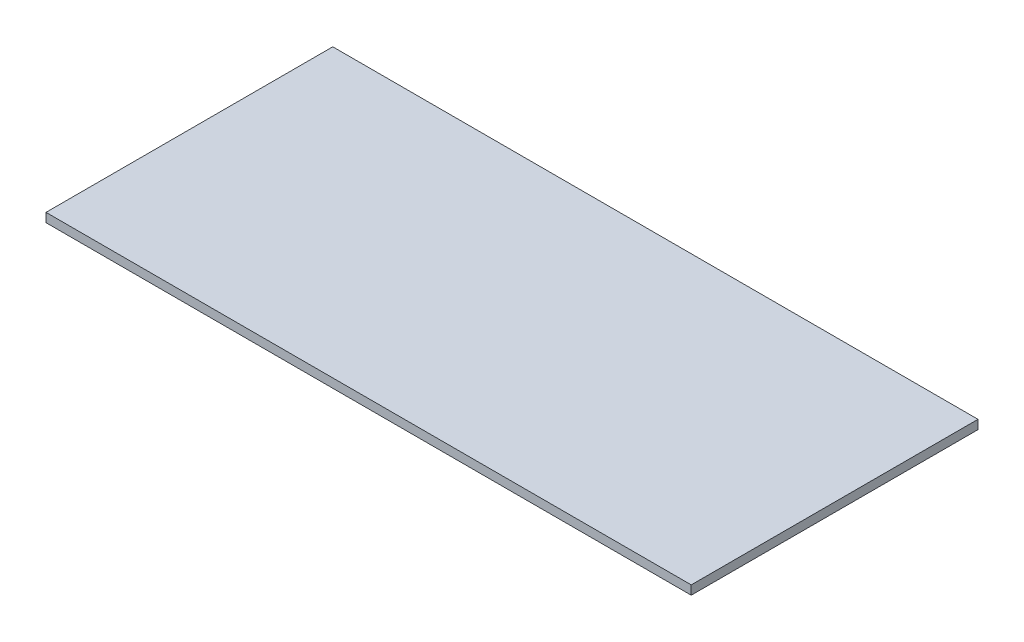
SolidWorks part; units mm, degrees
ref_plane "Front Plane" through (0, 0, 0) normal (0, 0, 1) x (1, 0, 0)
ref_plane "Top Plane" through (0, 0, 0) normal (0, 1, 0) x (1, 0, 0)
ref_plane "Right Plane" through (0, 0, 0) normal (1, 0, 0) x (0, 0, -1)
sketch "Sketch1" plane through (0, 0, 0) normal (0, 1, 0) x (1, 0, 0)
  line L1 (228.6, -101.6) -> (-228.6, -101.6)
  line L2 (228.6, -101.6) -> (228.6, 101.6)
  line L3 (228.6, 101.6) -> (-228.6, 101.6)
  line L4 (-228.6, -101.6) -> (-228.6, 101.6)
  line L5 (228.6, -101.6) -> (-228.6, 101.6) construction
  line L6 (228.6, 101.6) -> (-228.6, -101.6) construction
  point P0 (0, 0)
  dimension "D1" = 457.2
  dimension "D2" = 203.2
extrude "Boss-Extrude1" add sketch "Sketch1" along normal blind 6.35
